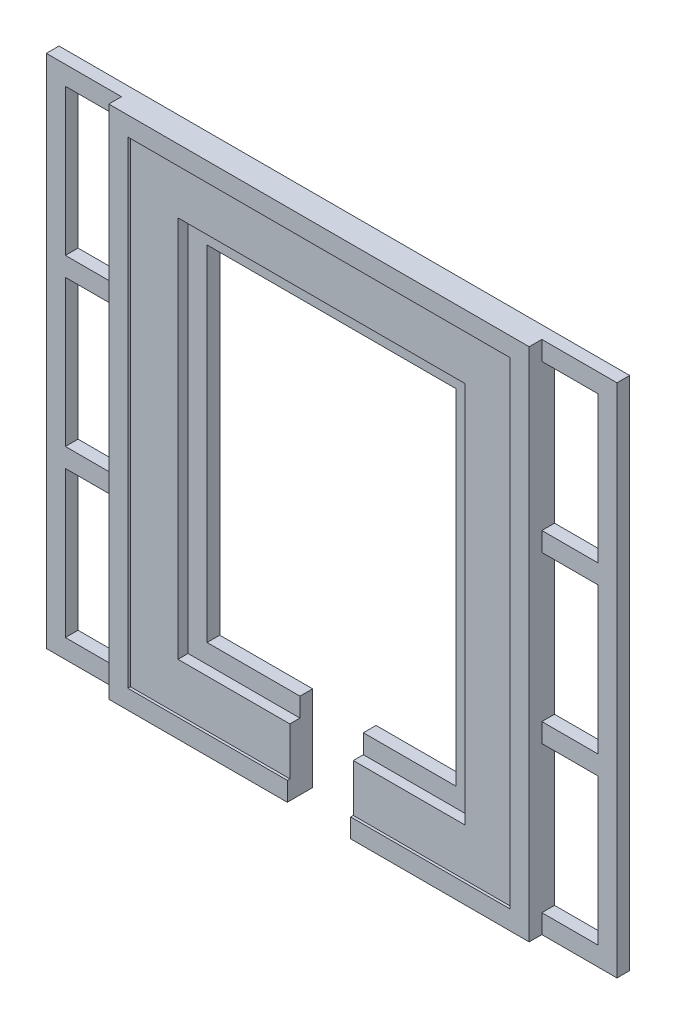
SolidWorks part; units mm, degrees
ref_plane "Front Plane" through (0, 0, 0) normal (0, 0, 1) x (1, 0, 0)
ref_plane "Top Plane" through (0, 0, 0) normal (0, 1, 0) x (1, 0, 0)
ref_plane "Right Plane" through (0, 0, 0) normal (1, 0, 0) x (0, 0, -1)
sketch "Sketch1" plane through (0, 0, 0) normal (0, 0, 1) x (1, 0, 0)
  line L0 (45, 81.3) -> (45, 0) construction
  line L1 (0, 0) -> (90, 0)
  line L2 (0, 0) -> (0, 81.3)
  line L3 (0, 81.3) -> (90, 81.3)
  line L4 (90, 0) -> (90, 81.3)
  line L5 (87, 3) -> (78.15, 3)
  line L6 (3, 78.3) -> (11.85, 78.3)
  line L7 (3, 78.3) -> (3, 55.2)
  line L8 (3, 55.2) -> (11.85, 55.2)
  line L9 (11.85, 78.3) -> (11.85, 55.2)
  line L10 (3, 52.2) -> (11.85, 52.2)
  line L11 (3, 52.2) -> (3, 29.1)
  line L12 (3, 29.1) -> (11.85, 29.1)
  line L13 (11.85, 52.2) -> (11.85, 29.1)
  line L14 (3, 26.1) -> (11.85, 26.1)
  line L15 (3, 26.1) -> (3, 3)
  line L16 (3, 3) -> (11.85, 3)
  line L17 (11.85, 26.1) -> (11.85, 3)
  line L18 (14.85, 78.3) -> (75.15, 78.3)
  line L19 (14.85, 78.3) -> (14.85, 3)
  line L20 (14.85, 3) -> (75.15, 3)
  line L21 (75.15, 78.3) -> (75.15, 3)
  line L22 (78.15, 26.1) -> (78.15, 3)
  line L23 (87, 26.1) -> (87, 3)
  line L24 (87, 26.1) -> (78.15, 26.1)
  line L25 (78.15, 52.2) -> (78.15, 29.1)
  line L26 (87, 52.2) -> (87, 29.1)
  line L27 (87, 52.2) -> (78.15, 52.2)
  line L28 (87, 55.2) -> (78.15, 55.2)
  line L29 (78.15, 78.3) -> (78.15, 55.2)
  line L30 (87, 78.3) -> (87, 55.2)
  line L31 (87, 78.3) -> (78.15, 78.3)
  line L32 (78.15, 29.1) -> (87, 29.1)
  line L33 (0, 40.65) -> (90, 40.65) construction
  line L34 (22.35, 70.8) -> (67.65, 70.8)
  line L35 (22.35, 70.8) -> (22.35, 10.5)
  line L36 (22.35, 10.5) -> (67.65, 10.5)
  line L37 (67.65, 70.8) -> (67.65, 10.5)
  line L38 (11.85, 55.2) -> (11.85, 52.2)
  line L39 (11.85, 29.1) -> (11.85, 26.1)
  line L40 (11.85, 78.3) -> (11.85, 81.3)
  line L41 (78.15, 78.3) -> (78.15, 81.3)
  line L42 (78.15, 55.2) -> (78.15, 52.2)
  line L43 (78.15, 29.1) -> (78.15, 26.1)
  line L44 (78.15, 3) -> (78.15, 0)
  line L45 (11.85, 3) -> (11.85, 0)
  line L46 (40, 13.5) -> (40, 0)
  line L47 (50, 13.5) -> (50, 0)
  line L49 (25.35, 67.8) -> (64.65, 67.8)
  line L50 (25.35, 67.8) -> (25.35, 13.5)
  line L51 (25.35, 13.5) -> (64.65, 13.5)
  line L52 (64.65, 67.8) -> (64.65, 13.5)
  point P41 (22.35, 40.65)
  point P42 (45, 70.8)
  dimension "D1" = 3
  dimension "D2" = 3
  dimension "D3" = 3
  dimension "D4" = 3
  dimension "D5" = 3
  dimension "D6" = 60.3
  dimension "D7" = 45.3
  dimension "D8" = 3
  dimension "D9" = 3
  dimension "D10" = 3
  dimension "D11" = 3
  dimension "D12" = 60.3
  dimension "D13" = 75.3
  dimension "D14" = 90
  dimension "D15" = 5
  dimension "D16" = 3
  dimension "D17" = 3
  dimension "D18" = 3
  dimension "D19" = 3
extrude "Boss-Extrude1" add sketch "Sketch1" along normal blind 2 contours L45 L16 L15 L14 L39 L12 L11 L10 L38 L8 L7 L6 L40 L3 L2 L1 | L20 L47 L1 L44 L22 L43 L25 L42 L29 L41 L3 L40 L9 L38 L13 L39 L17 L45 L46 L19 L18 L21 | L36 L47 L20 L21 L18 L19 L46 L35 L34 L37 | L37 L34 L35 L36 L49 L52 L51 L50 | L5 L44 L1 L4 L3 L41 L31 L30 L28 L42 L27 L26 L32 L43 L24 L23 region at (0.8216, 40.65, 0) region at (12.8991, 1.5, 0) region at (27.425, 3.9647, 0) region at (84.075, 80.4784, 0) region at (31.175, 11.2542, 0)
extrude "Boss-Extrude2" add sketch "Sketch1<3>" along normal blind 3.59 contours L21 L18 L19 L20 L34 L37 L36 L35 region at (27.425, 3.9647, 0)
sketch "Sketch1<3>" plane through (0, 0, 0) normal (0, 0, 1) x (1, 0, 0) same geometry as "Sketch1"
extrude "Boss-Extrude3" add sketch "Sketch1<4>" along normal blind 4 contours L17 L45 L1 L44 L22 L43 L25 L42 L29 L41 L3 L40 L9 L38 L13 L39 L18 L21 L20 L19 region at (12.8991, 1.5, 0)
sketch "Sketch1<4>" plane through (0, 0, 0) normal (0, 0, 1) x (1, 0, 0) same geometry as "Sketch1"
